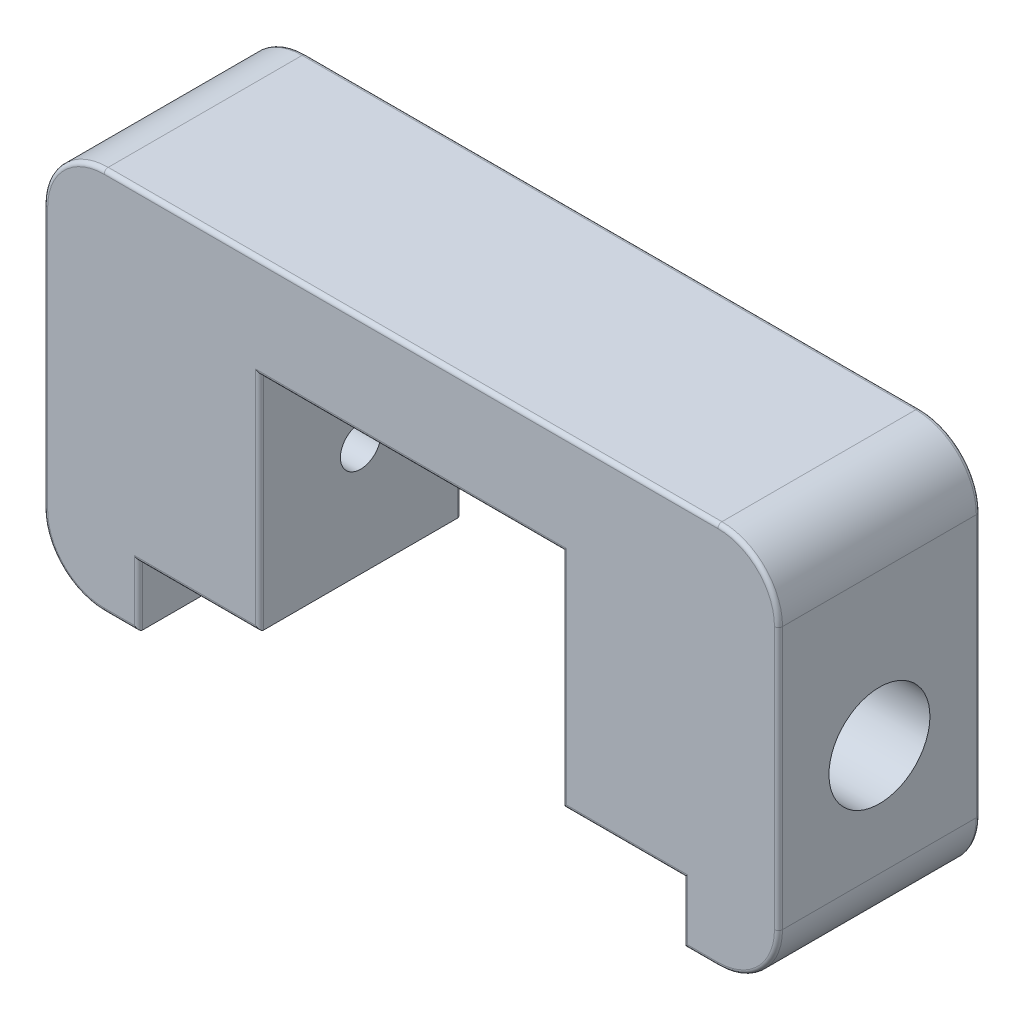
SolidWorks part; units mm, degrees
ref_plane "정면" through (0, 0, 0) normal (0, 0, 1) x (1, 0, 0)
ref_plane "윗면" through (0, 0, 0) normal (0, 1, 0) x (1, 0, 0)
ref_plane "우측면" through (0, 0, 0) normal (1, 0, 0) x (0, 0, -1)
sketch "스케치1" plane through (0, 0, 0) normal (0, 0, 1) x (1, 0, 0)
  line L1 (-18.2, 9.5) -> (18.2, 9.5)
  line L2 (-18.2, 9.5) -> (-18.2, -9.5)
  line L3 (-18.2, -9.5) -> (18.2, -9.5)
  line L4 (18.2, 9.5) -> (18.2, -9.5)
  line L5 (-18.2, 9.5) -> (18.2, -9.5) construction
  line L6 (-18.2, -9.5) -> (18.2, 9.5) construction
  line L7 (-7.5, 4.5) -> (7.5, 4.5)
  line L8 (-7.5, 4.5) -> (-7.5, -9.5)
  line L9 (-7.5, -9.5) -> (7.5, -9.5)
  line L10 (7.5, 4.5) -> (7.5, -9.5)
  line L11 (-7.5, 4.5) -> (7.5, -9.5) construction
  line L12 (-7.5, -9.5) -> (7.5, 4.5) construction
  line L13 (-7.5, -9.5) -> (-13.5, -9.5)
  line L14 (-7.5, -9.5) -> (-7.5, -6.5)
  line L15 (-7.5, -6.5) -> (-13.5, -6.5)
  line L16 (-13.5, -9.5) -> (-13.5, -6.5)
  line L17 (7.5, -9.5) -> (13.5, -9.5)
  line L18 (7.5, -9.5) -> (7.5, -6.5)
  line L19 (7.5, -6.5) -> (13.5, -6.5)
  line L20 (13.5, -9.5) -> (13.5, -6.5)
  point P0 (0, 0)
  point P6 (0, -2.5)
  dimension "D1" = 36.4
  dimension "D2" = 19
  dimension "D3" = 15
  dimension "D4" = 0
  dimension "D5" = 5
  dimension "D6" = 6
  dimension "D7" = 3
  dimension "D8" = 6
  dimension "D9" = 3
extrude "보스-돌출1" add sketch "스케치1" along normal blind 10 contours L20 L3 L4 L1 L2 L16 L15 L8 L7 L10 L19 region at (0, 9.0894, 0)
sketch "스케치2" plane through (18.2, 0, 0) normal (1, 0, 0) x (0, 0, -1)
  line L0 (-10, 4.5) -> (0, 4.5) construction
  line L1 (-10, 4.5) -> (0, 4.5) construction
  line L2 (-10, -6.5) -> (0, -6.5) construction
  line L3 (-10, -6.5) -> (0, -6.5) construction
  line L4 (0, 9.5) -> (0, -9.5) construction
  circle A0 centre (-5, -1) radius 1
  dimension "D1" = 2
  dimension "D2" = 5
  dimension "D3" = 5.5
extrude "컷-돌출1" cut sketch "스케치2" against normal through all
sketch "스케치3" plane through (18.2, 0, 0) normal (1, 0, 0) x (0, 0, -1)
  circle A0 centre (-5, -1) radius 2.5
  dimension "D1" = 5
extrude "컷-돌출2" cut sketch "스케치3" against normal blind 5
extrude "컷-돌출3" cut sketch "스케치3<2>" along normal blind 5 from surface contours A0 starting at face at (-18.2, 0, 5)
sketch "스케치3<2>" plane through (18.2, 0, 0) normal (1, 0, 0) x (0, 0, -1) same geometry as "스케치3"
fillet "필렛1" radius 3 4 edges at (-18.2, -9.5, 5) (18.2, -9.5, 5) (-18.2, 9.5, 5) (18.2, 9.5, 5)
fillet "필렛2" radius 0.2 32 edges at (-17.3213, 8.6213, 10) (0, 9.5, 10) (17.3213, 8.6213, 10) (18.2, 0, 10) (17.3213, -8.6213, 10) (14.35, -9.5, 10) (13.5, -8, 10) (10.5, -6.5, 10) (7.5, -1, 10) (0, 4.5, 10) (-7.5, -1, 10) (-10.5, -6.5, 10) (-13.5, -8, 10) (-14.35, -9.5, 10) (-17.3213, -8.6213, 10) (-18.2, 0, 10) (-13.5, -8, 0) (-10.5, -6.5, 0) (-7.5, -1, 0) (0, 4.5, 0) (7.5, -1, 0) (10.5, -6.5, 0) (13.5, -8, 0) (14.35, -9.5, 0) (17.3213, -8.6213, 0) (18.2, 0, 0) (17.3213, 8.6213, 0) (0, 9.5, 0) (-17.3213, 8.6213, 0) (-18.2, 0, 0) (-17.3213, -8.6213, 0) (-14.35, -9.5, 0)
